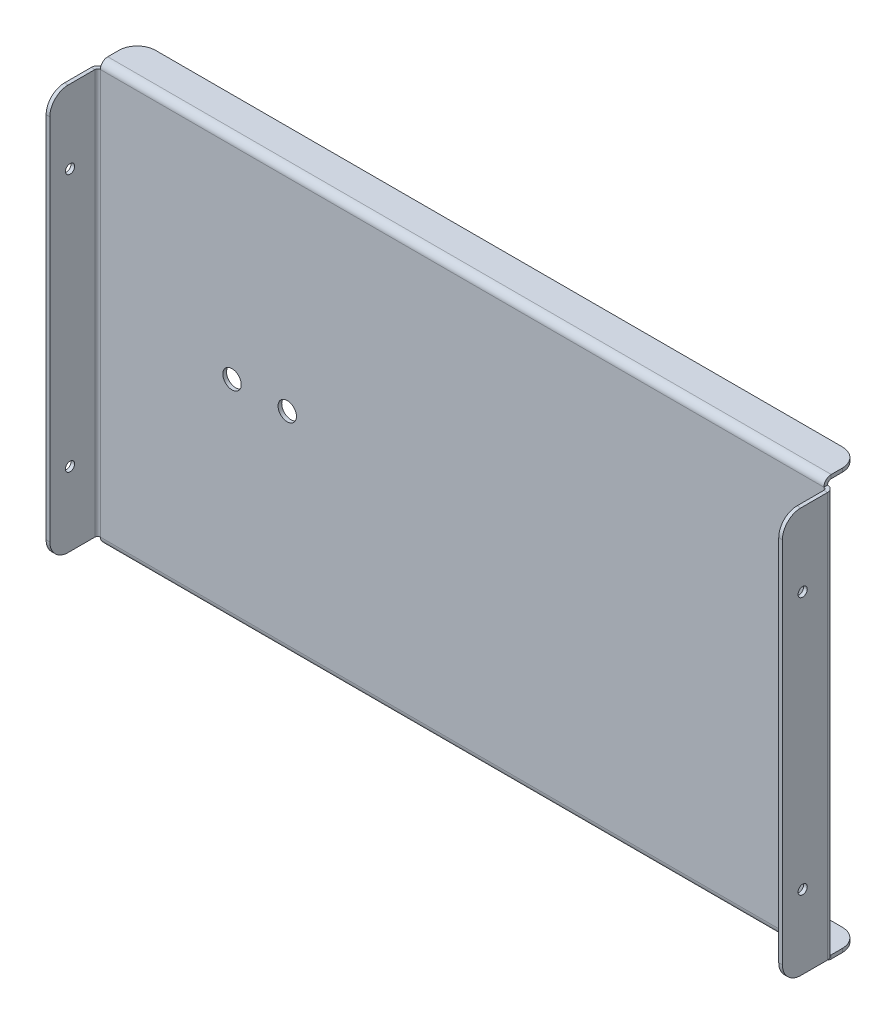
SolidWorks part; units mm, degrees
note: The reader was unsure of these and kept them because the rebuilt part matched: flange length of "Edge-Flange1", "Edge-Flange2", "Edge-Flange3".
material "ASTM A36 Steel"
ref_plane "Front Plane" through (0, 0, 0) normal (0, 0, 1) x (1, 0, 0)
ref_plane "Top Plane" through (0, 0, 0) normal (0, 1, 0) x (1, 0, 0)
ref_plane "Right Plane" through (0, 0, 0) normal (1, 0, 0) x (0, 0, -1)
sketch "Sketch1" plane through (0, 0, 0) normal (0, 0, 1) x (1, 0, 0)
  line L1 (-100, -55) -> (100, -55)
  line L2 (-100, -55) -> (-100, 55)
  line L3 (-100, 55) -> (100, 55)
  line L4 (100, -55) -> (100, 55)
  line L5 (-100, -55) -> (100, 55) construction
  line L6 (-100, 55) -> (100, -55) construction
  point P0 (0, 0)
  dimension "D1" = 110
  dimension "D2" = 200
base flange "Base-Flange1" sketch "Sketch1" thickness 1 reverse thickness direction no parameters "D1"=0.7366
edge flange "Edge-Flange1" sketch "Sketch8" flange angle 90 flange length 14 flange position material inside bend radius 0.7366 thickness 1 relief rectangular parameters "D6"=10
sketch "Sketch8" plane through (-100, 0, 0) normal (-1, 0, 0) x (0, -1, 0)
  line L0 (-55, 0) -> (55, 0) construction
  line L1 (-55, 0) -> (55, 0)
  line L2 (-55, 0) -> (-55, 13)
  line L3 (-55, 13) -> (55, 13)
  line L4 (55, 13) -> (55, 0)
bend "EdgeBend1" bend radius 0.7366 bend angle 90 parameters "D5"=1
edge flange "Edge-Flange2" sketch "Sketch13" flange angle 90 flange length 14 flange position material inside bend radius 0.7366 thickness 1 relief rectangular parameters "D6"=10
sketch "Sketch13" plane through (100, 0, 0) normal (1, 0, 0) x (0, 1, 0)
  line L0 (-55, 0) -> (55, 0) construction
  line L1 (-55, 0) -> (55, 0)
  line L2 (-55, 0) -> (-55, 13)
  line L3 (-55, 13) -> (55, 13)
  line L4 (55, 13) -> (55, 0)
bend "EdgeBend2" bend radius 0.7366 bend angle 90 parameters "D5"=2
sketch "Sketch14" plane through (-99, 0, 0) normal (1, 0, 0) x (0, 0, -1)
  line L0 (0, -55) -> (0, 55) construction
  line L1 (-0.7366, 55) -> (-0.7366, -55) construction
  circle A0 centre (-7.5, -35) radius 1.25
  circle A1 centre (-7.5, 35) radius 1.25
  point P8 (-0.7366, 0)
  dimension "D1" = 2.5
  dimension "D2" = 7.5
  dimension "D3" = 70
  dimension "D4" = 35
extrude "Cut-Extrude1" cut sketch "Sketch14" against normal blind 10 and the other way through all normal cut yes
edge flange "Edge-Flange3" sketch "Sketch17" flange profiles "Sketch17", "Sketch19" flange angle 90 flange length 10 flange position bend outside bend radius 1 thickness 1 relief rectangular parameters "D6"=10, "D8"=1
sketch "Sketch17" plane through (0, -55, -1) normal (0, -1, 0) x (-1, 0, 0)
  line L0 (98.2634, 0) -> (-98.2634, 0) construction
  line L1 (98.2634, 0) -> (-98.2634, 0)
  line L2 (-98.2634, 0) -> (-98.2634, 9)
  line L3 (-98.2634, 9) -> (98.2634, 9)
  line L4 (98.2634, 9) -> (98.2634, 0)
sketch "Sketch19" plane through (0, 55, -1) normal (0, 1, 0) x (1, 0, 0)
  line L0 (98.2634, 0) -> (-98.2634, 0) construction
  line L1 (98.2634, 0) -> (-98.2634, 0)
  line L2 (-98.2634, 0) -> (-98.2634, 9)
  line L3 (-98.2634, 9) -> (98.2634, 9)
  line L4 (98.2634, 9) -> (98.2634, 0)
bend "EdgeBend3" bend radius 1 bend angle 90 parameters "D5"=3
bend "EdgeBend4" bend radius 1 bend angle 90 parameters "D5"=5
fillet "Fillet1" radius 5 8 edges at (98.2634, -56.5, -10) (99.5, -55, 13) (99.5, 55, 13) (98.2634, 56.5, -10) (-98.2634, 56.5, -10) (-99.5, 55, 13) (-98.2634, -56.5, -10) (-99.5, -55, 13)
sketch "Sketch20" plane through (0, 0, -1) normal (0, 0, -1) x (-1, 0, 0)
  line L0 (-127.7655, 0) -> (146.2607, 0) construction
  circle A0 centre (47.5, 0) radius 2.5
  circle A1 centre (62.5, 0) radius 2.5
  dimension "D1" = 5
  dimension "D2" = 5
  dimension "D3" = 15
  dimension "D4" = 47.5
extrude "Cut-Extrude2" cut sketch "Sketch20" against normal through all normal cut yes
sketch "Bend-Lines1" [suppressed] plane through (0, 0, 0) normal (0, 1, 0) x (1, 0, 0)
sketch "Bounding-Box1" [suppressed] plane through (0, 0, 0) normal (0, 1, 0) x (1, 0, 0)
sheet metal parameters "Sheet-Metal1" thickness 1 parameters "D1"=0.7366
flat pattern "Flat-Pattern1" [suppressed]
sketch "Bend-Lines2" plane through (0, 0, 0) normal (0, 1, 0) x (1, 0, 0)
sketch3d "Bounding-Box2" [suppressed]
  line L0 (100, -55, 0) -> (-100, -55, 0) construction
  line L1 (100, 55, 0) -> (-100, 55, 0) construction
  line L2 (100, -55, 0) -> (100, 55, 0) construction
  line L3 (-100, -55, 0) -> (-100, 55, 0) construction
sheet metal parameters "Sheet-Metal2" thickness 1 parameters "D1"=0.7366
flat pattern "Flat-Pattern1"
sketch "Bend-Lines2" plane through (0, 0, 0) normal (0, 0, 1) x (1, 0, 0)
  line L0 (-99.2346, 55) -> (-99.2346, -55) construction
  line L1 (-99.2346, 55) -> (-99.2346, -55) construction
sketch3d "Bounding-Box2" [suppressed]
  line L0 (-112.4692, -55, 0) -> (100, -55, 0) construction
  line L1 (-112.4692, 55, 0) -> (100, 55, 0) construction
  line L2 (-112.4692, -55, 0) -> (-112.4692, 55, 0) construction
  line L3 (100, -55, 0) -> (100, 55, 0) construction
bend of the flat pattern "Flatten-<EdgeBend1>1"
sheet metal parameters "Sheet-Metal3" thickness 1 parameters "D1"=0.7366
flat pattern "Flat-Pattern1"
sketch "Bend-Lines2" plane through (0, 0, 0) normal (0, 0, 1) x (1, 0, 0)
  line L0 (-99.2346, 55) -> (-99.2346, -55) construction
  line L1 (-99.2346, 55) -> (-99.2346, -55) construction
  line L2 (99.2346, -55) -> (99.2346, 55) construction
  line L3 (99.2346, -55) -> (99.2346, 55) construction
sketch3d "Bounding-Box2" [suppressed]
  line L0 (-112.4692, -55, 0) -> (112.4692, -55, 0) construction
  line L1 (-112.4692, 55, 0) -> (112.4692, 55, 0) construction
  line L2 (-112.4692, -55, 0) -> (-112.4692, 55, 0) construction
  line L3 (112.4692, -55, 0) -> (112.4692, 55, 0) construction
bend of the flat pattern "Flatten-<EdgeBend1>1"
bend of the flat pattern "Flatten-<EdgeBend2>1"
sheet metal parameters "Sheet-Metal4" thickness 1 parameters "D1"=0.7366
flat pattern "Flat-Pattern1"
sketch "Bend-Lines2" plane through (0, 0, 0) normal (0, 0, 1) x (1, 0, 0)
  line L0 (-99.2346, 55) -> (-99.2346, -55) construction
  line L1 (-99.2346, 55) -> (-99.2346, -55) construction
  line L2 (99.2346, -55) -> (99.2346, 55) construction
  line L3 (99.2346, -55) -> (99.2346, 55) construction
sketch3d "Bounding-Box2" [suppressed]
  line L0 (-112.4692, -55, 0) -> (112.4692, -55, 0) construction
  line L1 (-112.4692, 55, 0) -> (112.4692, 55, 0) construction
  line L2 (-112.4692, -55, 0) -> (-112.4692, 55, 0) construction
  line L3 (112.4692, -55, 0) -> (112.4692, 55, 0) construction
bend of the flat pattern "Flatten-<EdgeBend1>1"
bend of the flat pattern "Flatten-<EdgeBend2>1"
sheet metal parameters "Sheet-Metal5" thickness 1 parameters "D1"=0.7366
flat pattern "Flat-Pattern1"
sketch "Bend-Lines2" plane through (0, 0, 0) normal (0, 0, 1) x (1, 0, 0)
  line L0 (-99.2346, 55) -> (-99.2346, -55) construction
  line L1 (-99.2346, 55) -> (-99.2346, -55) construction
  line L2 (99.2346, -55) -> (99.2346, 55) construction
  line L3 (99.2346, -55) -> (99.2346, 55) construction
  line L4 (-98.2634, -56.1781) -> (98.2634, -56.1781) construction
  line L5 (-98.2634, -56.1781) -> (98.2634, -56.1781) construction
  line L6 (98.2634, 56.1781) -> (-98.2634, 56.1781) construction
  line L7 (98.2634, 56.1781) -> (-98.2634, 56.1781) construction
sketch3d "Bounding-Box2" [suppressed]
  line L0 (-112.4692, 65.3562, 0) -> (112.4692, 65.3562, 0) construction
  line L1 (-112.4692, -65.3562, 0) -> (112.4692, -65.3562, 0) construction
  line L2 (-112.4692, 65.3562, 0) -> (-112.4692, -65.3562, 0) construction
  line L3 (112.4692, 65.3562, 0) -> (112.4692, -65.3562, 0) construction
bend of the flat pattern "Flatten-<EdgeBend1>1"
bend of the flat pattern "Flatten-<EdgeBend2>1"
bend of the flat pattern "Flatten-<EdgeBend3>1"
bend of the flat pattern "Flatten-<EdgeBend4>1"
sheet metal parameters "Sheet-Metal6" thickness 1 parameters "D1"=0.7366
flat pattern "Flat-Pattern1"
sketch "Bend-Lines2" plane through (0, 0, 0) normal (0, 0, 1) x (1, 0, 0)
  line L0 (-99.2346, 55) -> (-99.2346, -55) construction
  line L1 (-99.2346, 55) -> (-99.2346, -55) construction
  line L2 (99.2346, -55) -> (99.2346, 55) construction
  line L3 (99.2346, -55) -> (99.2346, 55) construction
  line L4 (-98.2634, -56.1781) -> (98.2634, -56.1781) construction
  line L5 (-98.2634, -56.1781) -> (98.2634, -56.1781) construction
  line L6 (98.2634, 56.1781) -> (-98.2634, 56.1781) construction
  line L7 (98.2634, 56.1781) -> (-98.2634, 56.1781) construction
sketch3d "Bounding-Box2" [suppressed]
  line L0 (-112.4692, 65.3562, 0) -> (112.4692, 65.3562, 0) construction
  line L1 (-112.4692, -65.3562, 0) -> (112.4692, -65.3562, 0) construction
  line L2 (-112.4692, 65.3562, 0) -> (-112.4692, -65.3562, 0) construction
  line L3 (112.4692, 65.3562, 0) -> (112.4692, -65.3562, 0) construction
bend of the flat pattern "Flatten-<EdgeBend1>1"
bend of the flat pattern "Flatten-<EdgeBend2>1"
bend of the flat pattern "Flatten-<EdgeBend3>1"
bend of the flat pattern "Flatten-<EdgeBend4>1"
